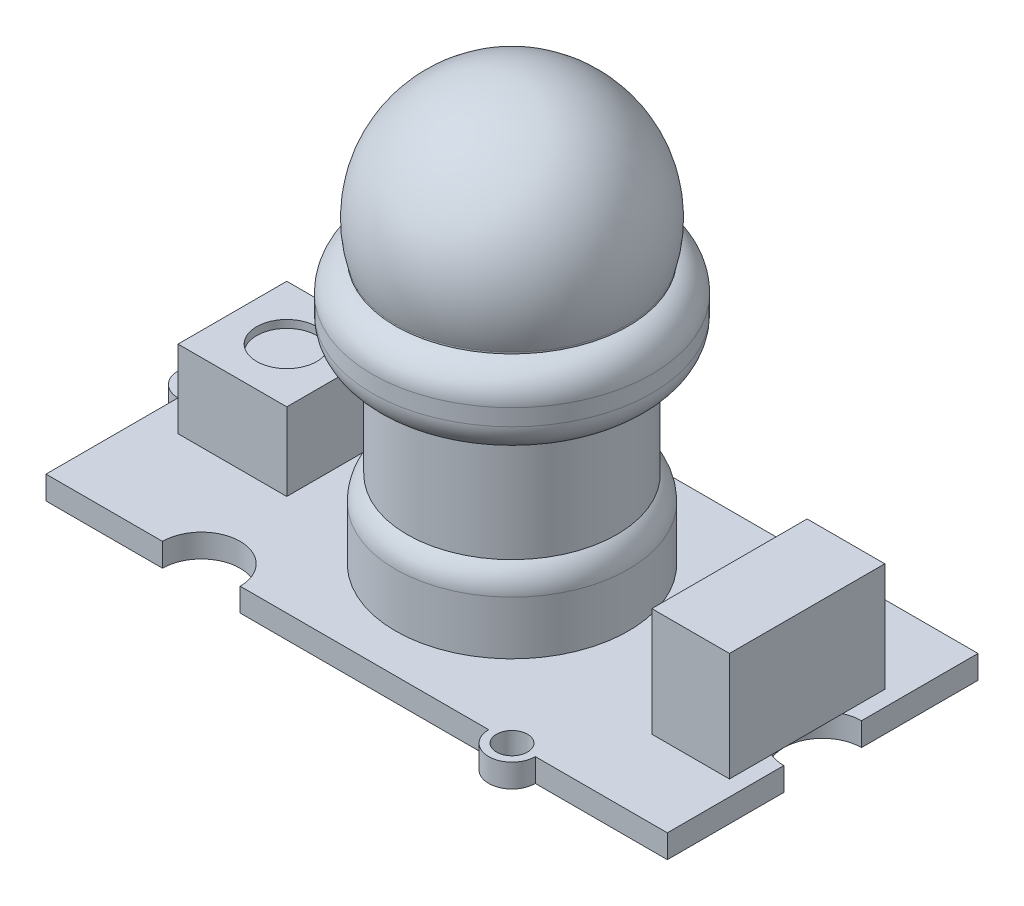
SolidWorks part; units mm, degrees
ref_plane "Front Plane" through (0, 0, 0) normal (0, 0, 1) x (1, 0, 0)
ref_plane "Top Plane" through (0, 0, 0) normal (0, 1, 0) x (1, 0, 0)
ref_plane "Right Plane" through (0, 0, 0) normal (1, 0, 0) x (0, 0, -1)
sketch "Sketch1" plane through (0, 0, 0) normal (0, 1, 0) x (1, 0, 0)
  line L1 (-20, 10) -> (20, 10)
  line L2 (-20, 10) -> (-20, -10)
  line L3 (-20, -10) -> (20, -10)
  line L4 (20, 10) -> (20, -10)
  line L5 (-20, 10) -> (20, -10) construction
  line L6 (-20, -10) -> (20, 10) construction
  point P0 (0, 0)
  dimension "D1" = 20
  dimension "D2" = 40
extrude "Boss-Extrude1" add sketch "Sketch1" along normal blind 1.5
sketch "Sketch2" plane through (0, 1.5, 0) normal (0, 1, 0) x (1, 0, 0)
  line L0 (-20, 10) -> (-20, -10) construction
  line L1 (20, 10) -> (-20, 10) construction
  line L2 (-20, -10) -> (20, -10) construction
  line L3 (20, -10) -> (20, 10) construction
  circle A0 centre (-20, 0) radius 1.5
  circle A1 centre (10, 10) radius 1.5
  circle A2 centre (10, -10) radius 1.5
  dimension "D1" = 3
  dimension "D2" = 3
  dimension "D3" = 3
  dimension "D4" = 10
  dimension "D5" = 10
extrude "Boss-Extrude2" add sketch "Sketch2" against normal blind 1.5
sketch "Sketch3" plane through (0, 1.5, 0) normal (0, 1, 0) x (1, 0, 0)
  line L0 (-20, -10) -> (8.5, -10) construction
  line L1 (8.5, 10) -> (-20, 10) construction
  line L2 (-20, -1.5) -> (-20, -10) construction
  line L3 (-20, 10) -> (-20, 1.5) construction
  line L4 (20, -10) -> (20, 10) construction
  line L5 (11.5, -10) -> (20, -10) construction
  circle A0 centre (-20, 0) radius 1
  circle A1 centre (10, -10) radius 1
  circle A2 centre (10, 10) radius 1
  circle A3 centre (-10, -10) radius 2.5
  circle A4 centre (-10, 10) radius 2.5
  circle A5 centre (20, 0) radius 2.5
  dimension "D1" = 2
  dimension "D2" = 2
  dimension "D3" = 2
  dimension "D4" = 5
  dimension "D5" = 5
  dimension "D7" = 10
  dimension "D8" = 5
  dimension "D9" = 10
  dimension "D6" = 10
extrude "Cut-Extrude1" cut sketch "Sketch3" against normal blind 1.5
sketch "Sketch4" plane through (0, 1.5, 0) normal (0, 1, 0) x (1, 0, 0)
  line L0 (-20, -10) -> (-12.5, -10) construction
  line L1 (-18, 3.5) -> (-11, 3.5)
  line L2 (-18, 3.5) -> (-18, -3.5)
  line L3 (-18, -3.5) -> (-11, -3.5)
  line L4 (-11, 3.5) -> (-11, -3.5)
  line L5 (-18, 3.5) -> (-11, -3.5) construction
  line L6 (-18, -3.5) -> (-11, 3.5) construction
  line L8 (-20, -1.5) -> (-20, -10) construction
  point P0 (-14.5, 0)
  dimension "D1" = 7
  dimension "D2" = 7
  dimension "D3" = 6.5
  dimension "D4" = 2
extrude "Boss-Extrude3" add sketch "Sketch4" along normal blind 5
sketch "Sketch5" plane through (0, 6.5, 0) normal (0, 1, 0) x (1, 0, 0)
  line L0 (-18, 3.5) -> (-18, -3.5) construction
  line L1 (-11, 3.5) -> (-18, 3.5) construction
  circle A0 centre (-14.5, 0) radius 1.9408
  dimension "D1" = 3.5
  dimension "D2" = 3.5
extrude "Cut-Extrude2" cut sketch "Sketch5" against normal blind 0.5
sketch "Sketch6" plane through (0, 1.5, 0) normal (0, 1, 0) x (1, 0, 0)
  line L0 (20, 2.5) -> (20, 10) construction
  line L1 (14, 5) -> (19, 5)
  line L2 (14, 5) -> (14, -5)
  line L3 (14, -5) -> (19, -5)
  line L4 (19, 5) -> (19, -5)
  line L5 (14, 5) -> (19, -5) construction
  line L6 (14, -5) -> (19, 5) construction
  line L7 (11.5, -10) -> (20, -10) construction
  point P0 (16.5, 0)
  dimension "D1" = 5
  dimension "D2" = 10
  dimension "D3" = 1
  dimension "D4" = 5
extrude "Boss-Extrude4" add sketch "Sketch6" along normal blind 7
sketch "Sketch7" plane through (0, 1.5, 0) normal (0, 1, 0) x (1, 0, 0)
  circle A0 centre (0, 0) radius 7.5
  dimension "D1" = 15
extrude "Boss-Extrude5" add sketch "Sketch7" along normal blind 5
sketch "Sketch8" plane through (0, 6.5, 0) normal (0, 1, 0) x (1, 0, 0)
  circle A0 centre (0, 0) radius 6.75
  dimension "D1" = 13.5
extrude "Boss-Extrude6" add sketch "Sketch8" along normal blind 7
sketch "Sketch9" plane through (0, 13.5, 0) normal (0, 1, 0) x (1, 0, 0)
  circle A0 centre (0, 0) radius 9
  dimension "D1" = 18
extrude "Boss-Extrude7" add sketch "Sketch9" along normal blind 5
sketch "Sketch11" plane through (0, 18.5, 0) normal (0, 1, 0) x (1, 0, 0)
  circle A0 centre (0, 0) radius 7.5
  dimension "D1" = 15
extrude "Boss-Extrude8" add sketch "Sketch11" along normal blind 0.1
dome "Dome1" faces to dome 1 distance 10 reverse direction no elliptical dome no face at (0, 18.6, 7.5) parameters "D1"=10
fillet "Fillet2" radius 2 2 edges at (0, 13.5, 9) (0, 18.5, 9)
fillet "Fillet4" radius 2 1 edges at (0, 6.5, 7.5)
